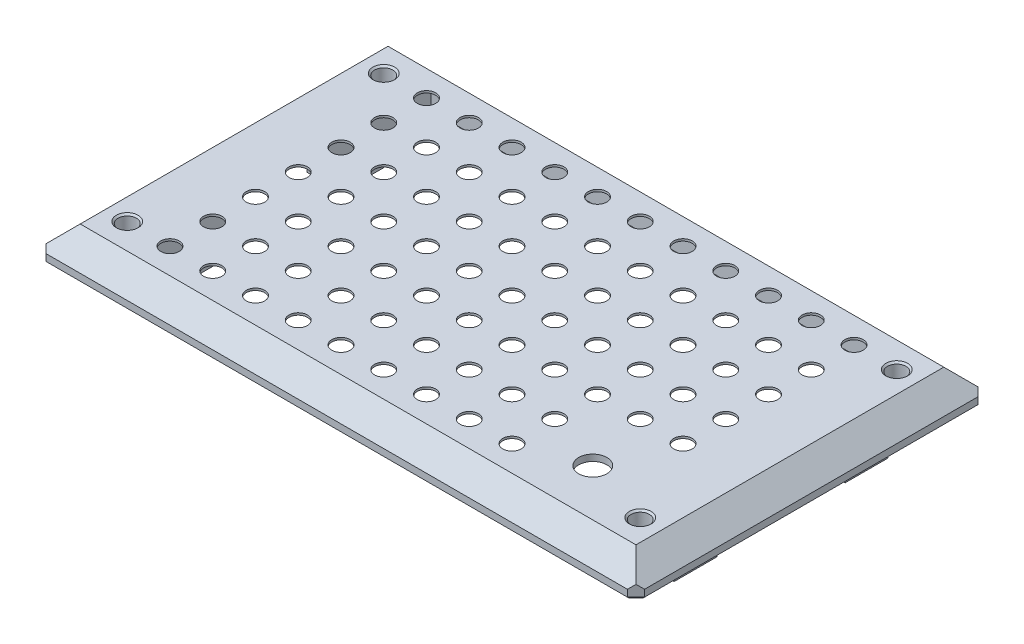
SolidWorks part; units mm, degrees
ref_plane "Front Plane" through (0, 0, 0) normal (0, 0, 1) x (1, 0, 0)
ref_plane "Top Plane" through (0, 0, 0) normal (0, 1, 0) x (1, 0, 0)
ref_plane "Right Plane" through (0, 0, 0) normal (1, 0, 0) x (0, 0, -1)
sketch "Sketch1" plane through (0, 0, 0) normal (0, 1, 0) x (1, 0, 0)
  line L1 (-70, -41) -> (70, -41)
  line L2 (-70, -41) -> (-70, 41)
  line L3 (-70, 41) -> (70, 41)
  line L4 (70, -41) -> (70, 41)
  line L5 (-70, -41) -> (70, 41) construction
  line L6 (-70, 41) -> (70, -41) construction
  point P0 (0, 0)
  dimension "D1" = 140
  dimension "D2" = 82
extrude "Boss-Extrude1" add sketch "Sketch1" along normal blind 2
sketch "Sketch2" plane through (0, 2, 0) normal (0, 1, 0) x (1, 0, 0)
  line L4 (70, -41) -> (70, 41)
  line L5 (70, 41) -> (-70, 41)
  line L6 (-70, 41) -> (-70, -41)
  line L7 (-70, -41) -> (70, -41)
  line L8 (70, -41) -> (70, 41)
  line L9 (70, 41) -> (-70, 41)
  line L10 (-70, 41) -> (-70, -41)
  line L11 (-70, -41) -> (70, -41)
  dimension "D1" = 0
ref_plane "Plane1" through (0, 7, 0) normal (0, 1, 0) x (1, 0, 0)
sketch "Sketch3" plane through (0, 7, 0) normal (0, 1, 0) x (1, 0, 0)
  line L0 (-70, 41) -> (-70, -41) construction
  line L1 (-65, -36) -> (65, -36)
  line L2 (-65, -36) -> (-65, 36)
  line L3 (-65, 36) -> (65, 36)
  line L4 (65, -36) -> (65, 36)
  line L5 (-65, -36) -> (65, 36) construction
  line L6 (-65, 36) -> (65, -36) construction
  line L7 (70, 41) -> (-70, 41) construction
  point P0 (0, 0)
  dimension "D1" = 5
  dimension "D2" = 5
loft "Loft1" add profiles "Sketch3", "Sketch2" connector at (-65, 7, 36) connector at (-70, 2, 41)
chamfer "Chamfer2" distance 2 angle 45 4 edges at (70, 1, 41) (70, 1, -41) (-70, 1, -41) (-70, 1, 41)
sketch "Sketch4" plane through (0, 0, 0) normal (0, -1, 0) x (1, 0, 0)
  line L0 (-70, -39) -> (-70, 39) construction
  line L1 (-62.9, 15) -> (-54.9, 15)
  line L2 (-62.9, 15) -> (-62.9, 25)
  line L3 (-62.9, 25) -> (-54.9, 25)
  line L4 (-54.9, 15) -> (-54.9, 25)
  line L5 (-62.9, 15) -> (-54.9, 25) construction
  line L6 (-62.9, 25) -> (-54.9, 15) construction
  line L7 (-70, 0) -> (70, 0) construction
  line L8 (70, 39) -> (70, -39) construction
  line L9 (0, 41) -> (0, -41) construction
  line L10 (-68, 41) -> (68, 41) construction
  line L11 (68, -41) -> (-68, -41) construction
  line L12 (-62.9, -25) -> (-54.9, -15) construction
  line L13 (-62.9, -15) -> (-54.9, -25) construction
  line L14 (-54.9, -15) -> (-54.9, -25)
  line L15 (-62.9, -25) -> (-54.9, -25)
  line L16 (-62.9, -15) -> (-62.9, -25)
  line L17 (-62.9, -15) -> (-54.9, -15)
  line L18 (62.9, -15) -> (54.9, -25) construction
  line L19 (62.9, -25) -> (54.9, -15) construction
  line L20 (62.9, 25) -> (54.9, 15) construction
  line L21 (62.9, 15) -> (54.9, 25) construction
  line L22 (62.9, -15) -> (54.9, -15)
  line L23 (62.9, -15) -> (62.9, -25)
  line L24 (62.9, -25) -> (54.9, -25)
  line L25 (54.9, -15) -> (54.9, -25)
  line L26 (54.9, 15) -> (54.9, 25)
  line L27 (62.9, 25) -> (54.9, 25)
  line L28 (62.9, 15) -> (62.9, 25)
  line L29 (62.9, 15) -> (54.9, 15)
  point P0 (-58.9, 20)
  point P21 (-58.9, -20)
  point P30 (58.9, -20)
  point P31 (58.9, 20)
  dimension "D1" = 10
  dimension "D2" = 7.1
  dimension "D3" = 8
  dimension "D4" = 40
extrude "Boss-Extrude2" add sketch "Sketch4" along normal blind 7
sketch "Sketch5" plane through (-62.9, 0, 0) normal (-1, 0, 0) x (0, 0, 1)
  line L0 (-15, 0) -> (-25, -7) construction
  line L1 (0, 0) -> (0, 50000) construction
  circle A0 centre (-20, -3.5) radius 2.05
  circle A1 centre (20, -3.5) radius 2.05
  dimension "D1" = 4.1
extrude "Cut-Extrude1" cut sketch "Sketch5" against normal through all
sketch "Sketch6" plane through (0, 0, 0) normal (0, -1, 0) x (1, 0, 0)
  line L0 (54.9, 25) -> (54.9, 15) construction
  line L1 (-53.9, -35) -> (53.9, -35)
  line L2 (-53.9, -35) -> (-53.9, 35)
  line L3 (-53.9, 35) -> (53.9, 35)
  line L4 (53.9, -35) -> (53.9, 35)
  line L5 (-53.9, -35) -> (53.9, 35) construction
  line L6 (-53.9, 35) -> (53.9, -35) construction
  line L8 (-65, 36) -> (65, 36) construction
  point P0 (0, 0)
  dimension "D1" = 1
  dimension "D2" = 1
extrude "Cut-Extrude2" cut sketch "Sketch6" against normal offset from surface (5.5 mm away) 1.5 up to face at (0, 7, 0)
sketch "Sketch7" plane through (0, 5.5, 0) normal (0, -1, 0) x (1, 0, 0)
  line L0 (0, 35) -> (0, -35) construction
  line L1 (-53.9, 35) -> (53.9, 35) construction
  line L2 (-53.9, -35) -> (53.9, -35) construction
  line L3 (-53.9, 0) -> (53.9, 0) construction
  line L4 (-53.9, -35) -> (-53.9, 35) construction
  line L5 (53.9, 35) -> (53.9, -35) construction
  circle A0 centre (0, 0) radius 2.15
  circle A1 centre (10, 0) radius 2.15
  circle A2 centre (20, 0) radius 2.15
  circle A3 centre (30, 0) radius 2.15
  circle A4 centre (40, 0) radius 2.15
  circle A5 centre (50, 0) radius 2.15
  circle A7 centre (10, 10) radius 2.15
  circle A8 centre (20, 10) radius 2.15
  circle A9 centre (30, 10) radius 2.15
  circle A10 centre (40, 10) radius 2.15
  circle A11 centre (50, 10) radius 2.15
  circle A13 centre (10, 20) radius 2.15
  circle A14 centre (20, 20) radius 2.15
  circle A15 centre (30, 20) radius 2.15
  circle A16 centre (40, 20) radius 2.15
  circle A17 centre (50, 20) radius 2.15
  circle A19 centre (10, 30) radius 2.15
  circle A20 centre (20, 30) radius 2.15
  circle A21 centre (30, 30) radius 2.15
  circle A22 centre (40, 30) radius 2.15
  circle A23 centre (50, 30) radius 2.15
  circle A25 centre (0, 10) radius 2.15
  circle A26 centre (0, 20) radius 2.15
  circle A27 centre (0, 30) radius 2.15
  circle A35 centre (-50, 30) radius 2.15
  circle A36 centre (-40, 30) radius 2.15
  circle A37 centre (-30, 30) radius 2.15
  circle A38 centre (-20, 30) radius 2.15
  circle A39 centre (-10, 30) radius 2.15
  circle A40 centre (-50, 20) radius 2.15
  circle A41 centre (-40, 20) radius 2.15
  circle A42 centre (-30, 20) radius 2.15
  circle A43 centre (-20, 20) radius 2.15
  circle A44 centre (-10, 20) radius 2.15
  circle A45 centre (-50, 10) radius 2.15
  circle A46 centre (-40, 10) radius 2.15
  circle A47 centre (-30, 10) radius 2.15
  circle A48 centre (-20, 10) radius 2.15
  circle A49 centre (-10, 10) radius 2.15
  circle A50 centre (-50, 0) radius 2.15
  circle A51 centre (-40, 0) radius 2.15
  circle A52 centre (-30, 0) radius 2.15
  circle A53 centre (-20, 0) radius 2.15
  circle A54 centre (-10, 0) radius 2.15
  circle A55 centre (-10, -10) radius 2.15
  circle A56 centre (-20, -10) radius 2.15
  circle A57 centre (-30, -10) radius 2.15
  circle A58 centre (-40, -10) radius 2.15
  circle A59 centre (-50, -10) radius 2.15
  circle A60 centre (-10, -20) radius 2.15
  circle A61 centre (-20, -20) radius 2.15
  circle A62 centre (-30, -20) radius 2.15
  circle A63 centre (-40, -20) radius 2.15
  circle A64 centre (-50, -20) radius 2.15
  circle A65 centre (-10, -30) radius 2.15
  circle A66 centre (-20, -30) radius 2.15
  circle A67 centre (-30, -30) radius 2.15
  circle A68 centre (-40, -30) radius 2.15
  circle A69 centre (-50, -30) radius 2.15
  circle A70 centre (0, -30) radius 2.15
  circle A71 centre (0, -20) radius 2.15
  circle A72 centre (0, -10) radius 2.15
  circle A73 centre (50, -30) radius 2.15
  circle A74 centre (40, -30) radius 2.15
  circle A75 centre (30, -30) radius 2.15
  circle A76 centre (20, -30) radius 2.15
  circle A77 centre (10, -30) radius 2.15
  circle A78 centre (50, -20) radius 2.15
  circle A79 centre (40, -20) radius 2.15
  circle A80 centre (30, -20) radius 2.15
  circle A81 centre (20, -20) radius 2.15
  circle A82 centre (10, -20) radius 2.15
  circle A83 centre (50, -10) radius 2.15
  circle A84 centre (40, -10) radius 2.15
  circle A85 centre (30, -10) radius 2.15
  circle A86 centre (20, -10) radius 2.15
  circle A87 centre (10, -10) radius 2.15
  dimension "D1" = 4.3
  dimension "D2" = 6
  dimension "D3" = 4
extrude "Cut-Extrude3" cut sketch "Sketch7" against normal through all
sketch "Sketch8" plane through (0, 5.5, 0) normal (0, -1, 0) x (1, 0, 0)
  line L0 (0, 35) -> (0, -35) construction
  line L1 (-53.9, 35) -> (53.9, 35) construction
  line L2 (53.9, -35) -> (-53.9, -35) construction
  line L3 (-53.9, 0) -> (53.9, 0) construction
  line L4 (-53.9, -35) -> (-53.9, 35) construction
  line L5 (53.9, -35) -> (53.9, 35) construction
  circle A0 centre (0, 0) radius 4.2
  circle A1 centre (10, 0) radius 4.2
  circle A2 centre (20, 0) radius 4.2
  circle A3 centre (30, 0) radius 4.2
  circle A4 centre (40, 0) radius 4.2
  circle A5 centre (50, 0) radius 4.2
  circle A6 centre (10, 10) radius 4.2
  circle A7 centre (20, 10) radius 4.2
  circle A8 centre (30, 10) radius 4.2
  circle A9 centre (40, 10) radius 4.2
  circle A10 centre (50, 10) radius 4.2
  circle A11 centre (10, 20) radius 4.2
  circle A12 centre (20, 20) radius 4.2
  circle A13 centre (30, 20) radius 4.2
  circle A14 centre (40, 20) radius 4.2
  circle A15 centre (50, 20) radius 4.2
  circle A16 centre (10, 30) radius 4.2
  circle A17 centre (20, 30) radius 4.2
  circle A18 centre (30, 30) radius 4.2
  circle A19 centre (40, 30) radius 4.2
  circle A20 centre (50, 30) radius 4.2
  circle A21 centre (0, 10) radius 4.2
  circle A22 centre (0, 20) radius 4.2
  circle A23 centre (0, 30) radius 4.2
  circle A24 centre (0, -30) radius 4.2
  circle A25 centre (0, -20) radius 4.2
  circle A26 centre (0, -10) radius 4.2
  circle A27 centre (50, -30) radius 4.2
  circle A28 centre (40, -30) radius 4.2
  circle A29 centre (30, -30) radius 4.2
  circle A30 centre (20, -30) radius 4.2
  circle A31 centre (10, -30) radius 4.2
  circle A32 centre (50, -20) radius 4.2
  circle A33 centre (40, -20) radius 4.2
  circle A34 centre (30, -20) radius 4.2
  circle A35 centre (20, -20) radius 4.2
  circle A36 centre (10, -20) radius 4.2
  circle A37 centre (50, -10) radius 4.2
  circle A38 centre (40, -10) radius 4.2
  circle A39 centre (30, -10) radius 4.2
  circle A40 centre (20, -10) radius 4.2
  circle A41 centre (10, -10) radius 4.2
  circle A42 centre (-10, -10) radius 4.2
  circle A43 centre (-20, -10) radius 4.2
  circle A44 centre (-30, -10) radius 4.2
  circle A45 centre (-40, -10) radius 4.2
  circle A46 centre (-50, -10) radius 4.2
  circle A47 centre (-10, -20) radius 4.2
  circle A48 centre (-20, -20) radius 4.2
  circle A49 centre (-30, -20) radius 4.2
  circle A50 centre (-40, -20) radius 4.2
  circle A51 centre (-50, -20) radius 4.2
  circle A52 centre (-10, -30) radius 4.2
  circle A53 centre (-20, -30) radius 4.2
  circle A54 centre (-30, -30) radius 4.2
  circle A55 centre (-40, -30) radius 4.2
  circle A56 centre (-50, -30) radius 4.2
  circle A57 centre (-50, 30) radius 4.2
  circle A58 centre (-40, 30) radius 4.2
  circle A59 centre (-30, 30) radius 4.2
  circle A60 centre (-20, 30) radius 4.2
  circle A61 centre (-10, 30) radius 4.2
  circle A62 centre (-50, 20) radius 4.2
  circle A63 centre (-40, 20) radius 4.2
  circle A64 centre (-30, 20) radius 4.2
  circle A65 centre (-20, 20) radius 4.2
  circle A66 centre (-10, 20) radius 4.2
  circle A67 centre (-50, 10) radius 4.2
  circle A68 centre (-40, 10) radius 4.2
  circle A69 centre (-30, 10) radius 4.2
  circle A70 centre (-20, 10) radius 4.2
  circle A71 centre (-10, 10) radius 4.2
  circle A72 centre (-50, 0) radius 4.2
  circle A73 centre (-40, 0) radius 4.2
  circle A74 centre (-30, 0) radius 4.2
  circle A75 centre (-20, 0) radius 4.2
  circle A76 centre (-10, 0) radius 4.2
  dimension "D1" = 8.4
  dimension "D2" = 6
  dimension "D3" = 4
extrude "Cut-Extrude4" cut sketch "Sketch8" against normal blind 1
sketch "Sketch9" plane through (0, 7, 0) normal (0, 1, 0) x (1, 0, 0)
  line L1 (53.9, -35) -> (34.6, -35)
  line L2 (53.9, -35) -> (53.9, -15.5)
  line L3 (53.9, -15.5) -> (34.6, -15.5)
  line L4 (34.6, -35) -> (34.6, -15.5)
  dimension "D1" = 19.3
  dimension "D2" = 19.5
sketch "Sketch13" plane through (0, 5.5, 0) normal (0, -1, 0) x (1, 0, 0)
  circle A0 centre (50, 20) radius 4.2 construction
  circle A1 centre (40, 20) radius 4.2 construction
  circle A2 centre (40, 30) radius 4.2 construction
  circle A3 centre (50, 30) radius 4.2 construction
  circle A4 centre (50, 20) radius 4.2
  circle A5 centre (40, 20) radius 4.2
  circle A6 centre (40, 30) radius 4.2
  circle A7 centre (50, 30) radius 4.2
extrude "Boss-Extrude4" add sketch "Sketch13" against normal up to surface (1.5 mm away) up to face at (-30, 7, -2.15)
sketch "Sketch10" plane through (0, 5.5, 0) normal (0, -1, 0) x (1, 0, 0)
  line L1 (53.9, 35) -> (43.9, 35) construction
  line L2 (53.9, 35) -> (53.9, 25) construction
  line L3 (53.9, 25) -> (43.9, 25) construction
  line L4 (43.9, 35) -> (43.9, 25) construction
  circle A0 centre (43.9, 25) radius 3.3
  dimension "D1" = 6.6
  dimension "D2" = 10
extrude "Cut-Extrude5" cut sketch "Sketch10" against normal through all
sketch "Sketch11" plane through (0, 0, 0) normal (0, -1, 0) x (1, 0, 0)
  line L0 (53.9, 35) -> (53.9, 11.5588) construction
  line L1 (53.9, 10) -> (63.9, 10)
  line L2 (53.9, 10) -> (53.9, -10)
  line L3 (53.9, -10) -> (63.9, -10)
  line L4 (63.9, 10) -> (63.9, -10)
  line L5 (-53.9, 35) -> (-53.9, -35) construction
  line L6 (-53.9, 10) -> (-63.9, 10)
  line L7 (-53.9, 10) -> (-53.9, -10)
  line L8 (-53.9, -10) -> (-63.9, -10)
  line L9 (-63.9, 10) -> (-63.9, -10)
  line L10 (-70, -39) -> (-70, 39) construction
  point P12 (-63.9, 0)
  point P15 (-70, 0)
  point P16 (63.9, 0)
  dimension "D1" = 10
  dimension "D2" = 20
extrude "Cut-Extrude6" cut sketch "Sketch11" against normal up to surface (5.5 mm away) up to face at (43.9, 5.5, 21.7)
sketch "Sketch12" plane through (0, 0, 0) normal (0, -1, 0) x (1, 0, 0)
  line L0 (0, 0) -> (-60, 0) construction
  line L1 (-60, -30) -> (-60, 30) construction
  line L2 (-70, -39) -> (-70, 39) construction
  line L3 (0, 41) -> (0, -41) construction
  line L4 (-68, 41) -> (68, 41) construction
  line L5 (68, -41) -> (-68, -41) construction
  line L6 (60, -30) -> (60, 30) construction
  circle A0 centre (-60, 30) radius 2.15
  circle A1 centre (-60, -30) radius 2.15
  circle A2 centre (60, -30) radius 2.15
  circle A3 centre (60, 30) radius 2.15
  point P6 (-60, 0)
  point P20 (60, 0)
  dimension "D1" = 4.3
  dimension "D2" = 60
  dimension "D3" = 10
extrude "Cut-Extrude7" cut sketch "Sketch12" against normal through all
chamfer "Chamfer3" distance 0.4 angle 45 8 edges at (-69, 0, -40) (-70, 0, 0) (-69, 0, 40) (0, 0, 41) (69, 0, 40) (70, 0, 0) (69, 0, -40) (0, 0, -41)
chamfer "Chamfer4" distance 0.4 angle 45 4 edges at (60, 7, 27.85) (60, 7, -32.15) (-60, 7, 27.85) (-60, 7, -32.15)
chamfer "Chamfer5" distance 0.4 angle 45 4 edges at (-62.9, -3.5, 17.95) (-62.9, -3.5, -17.95) (62.9, -3.5, 22.05) (62.9, -3.5, -17.95)
